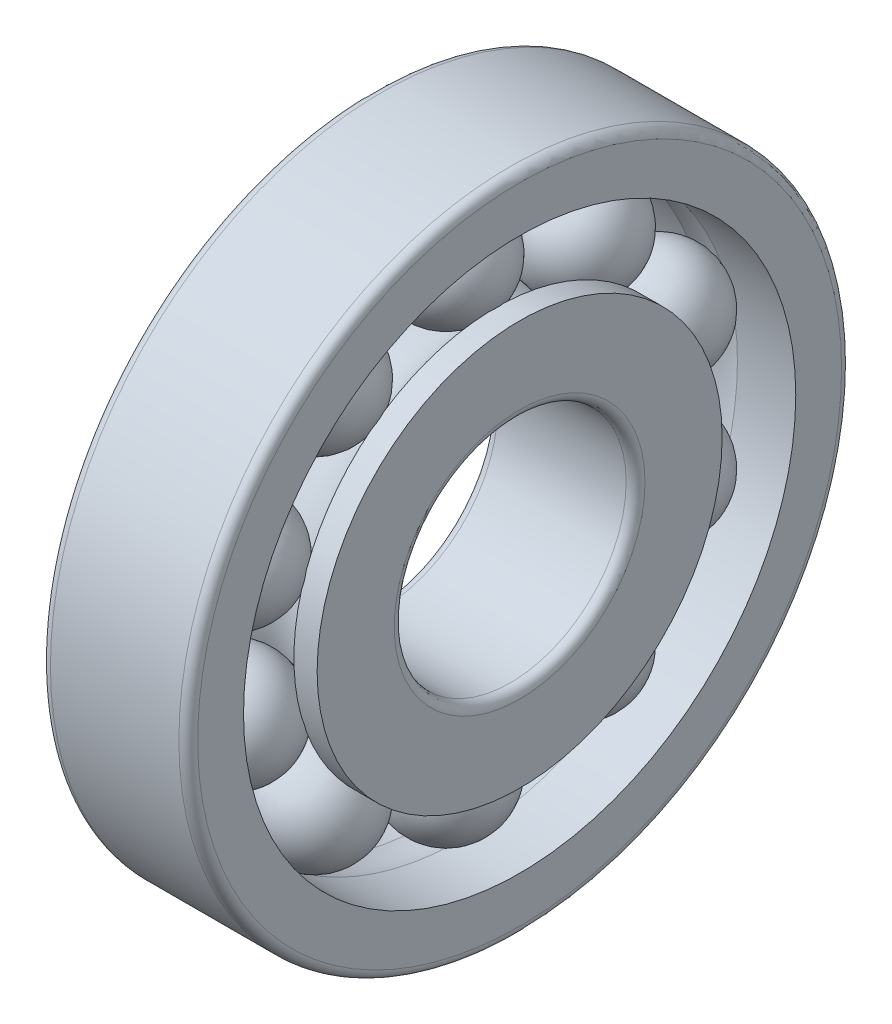
SolidWorks part; units mm, degrees
ref_plane "Plane1" through (0, 0, 0) normal (0, 0, 1) x (1, 0, 0)
ref_plane "Plane2" through (0, 0, 0) normal (0, 1, 0) x (1, 0, 0)
ref_plane "Plane3" through (0, 0, 0) normal (1, 0, 0) x (0, 0, -1)
other "Configuration Table"
sketch "Clipboard" plane through (0, 0, 0) normal (0, 0, 1) x (1, 0, 0)
  line L0 (-10, 0) -> (10, 0) construction
  line L1 (0, 0) -> (22.021, -3.8829)
  line L2 (0, 0) -> (9.4972, 1.6746)
  line L3 (0, 0) -> (-3.8829, -22.021)
  line L4 (0, 0) -> (-22.3573, -0.3902)
  dimension "BallCLRad" = 9.6438
sketch "CagSpiSke" plane through (0, 0, 0) normal (0, 0, 1) x (1, 0, 0)
  line L0 (0.2381, 9.2469) -> (0.2381, 10.0406)
  line L1 (0.2381, 10.0406) -> (-0.2381, 10.0406)
  line L2 (-0.2381, 10.0406) -> (-0.2381, 9.2469)
  line L3 (-0.2381, 9.2469) -> (0.2381, 9.2469)
  line L4 (-20.6375, 0) -> (20.6375, 0) construction
  line L5 (0, 0) -> (0, 23.7692) construction
  dimension "OD" = 20.0813
  dimension "ID" = 18.4937
revolve "CageSpine" add sketch "CagSpiSke" angle 0.001 about L4
ref_axis "Axis1" through (-50, 0, 0) along (1, 0, 0)
sketch "CagBalSke" plane through (0, 0, 0) normal (0, 0, 1) x (1, 0, 0)
  line L0 (-2.6194, 9.6438) -> (2.6194, 9.6438)
  line L1 (-1.905, 9.6438) -> (1.905, 9.6438) construction
  line L2 (-10, 0) -> (10, 0) construction
  line L3 (0, 0) -> (0, 24) construction
  arc A0 (2.6194, 9.6438) -> (-2.6194, 9.6438) centre (0, 9.6438) cw
  dimension "BallCLRad" = 9.6438
revolve "CageBall" [suppressed] add sketch "CagBalSke" angle 360 about L1 reverse direction yes
pattern_circular "CageBalls" [suppressed] count 10 every 36 about axis through (-50, 0, 0) along (1, 0, 0)
sketch "CagTrmODSke" plane through (0, 0, 0) normal (0, 0, 1) x (1, 0, 0)
  line L0 (2.6204, 10.0406) -> (2.6204, 12.2641)
  line L1 (2.6204, 12.2641) -> (-2.6204, 12.2641)
  line L2 (-2.6204, 12.2641) -> (-2.6204, 10.0406)
  line L3 (-2.6204, 10.0406) -> (2.6204, 10.0406)
  line L4 (-20.6375, 0) -> (20.6375, 0) construction
  line L5 (0, 0) -> (0, 25) construction
  dimension "Width" = 5.2408
  dimension "ID" = 20.0813
  dimension "OD" = 24.5282
revolve "CageTrimOD" [suppressed] cut sketch "CagTrmODSke" angle 360 about L4 reverse direction yes
sketch "CagTrmIDSke" plane through (0, 0, 0) normal (0, 0, 1) x (1, 0, 0)
  line L0 (2.6204, 7.0254) -> (2.6204, 9.2469)
  line L1 (2.6204, 9.2469) -> (-2.6204, 9.2469)
  line L2 (-2.6204, 9.2469) -> (-2.6204, 7.0254)
  line L3 (-2.6204, 7.0254) -> (2.6204, 7.0254)
  line L4 (-20.6375, 0) -> (20.6375, 0) construction
  line L5 (0, 0) -> (0, 25) construction
  dimension "Width" = 5.2408
  dimension "ID" = 14.0508
  dimension "OD" = 18.4938
revolve "CageTrimID" [suppressed] cut sketch "CagTrmIDSke" angle 360 about L4 reverse direction yes
sketch "BalSimSke" plane through (0, 0, 0) normal (0, 0, 1) x (1, 0, 0)
  line L0 (-10, 0) -> (10, 0) construction
  line L1 (-10, 9.6438) -> (10, 9.6438) construction
  line L2 (0, 0) -> (0, 23) construction
  circle A0 centre (0, 9.6438) radius 2.3812
  dimension "BallCLRad" = 9.6438
  dimension "Ball_diameter" = 4.7625
revolve "BallsSimplified" [suppressed] add sketch "BalSimSke" angle 360 about L0
sketch "BalDetSke" plane through (0, 0, 0) normal (0, 0, 1) x (1, 0, 0)
  line L0 (-2.3813, 9.6438) -> (2.3813, 9.6438)
  line L1 (-1.905, 9.6438) -> (1.905, 9.6438) construction
  line L2 (0, 0) -> (0, 25) construction
  arc A0 (2.3813, 9.6438) -> (-2.3813, 9.6438) centre (0, 9.6438) cw
  dimension "BallCLRad" = 9.6438
  dimension "Ball_diameter" = 4.7625
revolve "BallDetailed" add sketch "BalDetSke" angle 360 about L1 reverse direction yes
sketch "InnRacSke" plane through (0, 0, 0) normal (0, 0, 1) x (1, 0, 0)
  line L0 (-2.1724, 8.7312) -> (-3.175, 8.7312)
  line L1 (-3.175, 8.7312) -> (-3.175, 5.4064)
  line L2 (-2.7686, 5) -> (2.7686, 5)
  line L3 (3.175, 5.4064) -> (3.175, 8.7312)
  line L4 (3.175, 8.7312) -> (2.1724, 8.7312)
  line L5 (-20.6375, 0) -> (20.6375, 0) construction
  line L6 (0, 0) -> (0, 30) construction
  arc A0 (-3.175, 5.4064) -> (-2.7686, 5) centre (-2.7686, 5.4064) ccw
  arc A1 (2.7686, 5) -> (3.175, 5.4064) centre (2.7686, 5.4064) ccw
  arc A2 (2.1724, 8.7312) -> (-2.1724, 8.7312) centre (0, 9.6438) cw
  dimension "BallCLRad" = 9.6438
  dimension "Fillet_radius" = 0.4064
  dimension "Ball_diameter" = 4.7125
  dimension "ID" = 10
  dimension "OD" = 17.4625
  dimension "Width" = 6.35
revolve "InnerRace" add sketch "InnRacSke" angle 360 about L5 reverse direction yes
sketch "OutRacSke" plane through (0, 0, 0) normal (0, 0, 1) x (1, 0, 0)
  line L0 (-0.658, 11.9063) -> (-3.175, 11.9062)
  line L1 (-3.175, 11.9062) -> (-3.175, 13.8811)
  line L2 (-2.7686, 14.2875) -> (2.7686, 14.2875)
  line L3 (3.175, 13.8811) -> (3.175, 11.9062)
  line L4 (3.175, 11.9062) -> (0.658, 11.9063)
  line L5 (-20.6375, 0) -> (20.6375, 0) construction
  line L6 (0, 0) -> (0, 30) construction
  arc A0 (-3.175, 13.8811) -> (-2.7686, 14.2875) centre (-2.7686, 13.8811) cw
  arc A1 (2.7686, 14.2875) -> (3.175, 13.8811) centre (2.7686, 13.8811) cw
  arc A2 (0.658, 11.9063) -> (-0.658, 11.9063) centre (0, 9.6438) ccw
  dimension "BallCLRad" = 9.6438
  dimension "Fillet_radius" = 0.4064
  dimension "Ball_diameter" = 4.7125
  dimension "Width" = 6.35
revolve "OuterRace" add sketch "OutRacSke" angle 360 about L5 reverse direction yes
pattern_circular "BallsDetailed" count 10 every 36 about axis through (-50, 0, 0) along (1, 0, 0) of "BallDetailed"
equation "\"BallCLRad@Clipboard\" = ( \"OD@OutRacSke\" + \"ID@InnRacSke\" ) / 4"
equation "\"BallCLRad@BalSimSke\" = \"BallCLRad@Clipboard\""
equation "\"BallCLRad@BalDetSke\" = \"BallCLRad@Clipboard\""
equation "\"BallCLRad@InnRacSke\" = \"BallCLRad@Clipboard\""
equation "\"BallCLRad@OutRacSke\" = \"BallCLRad@Clipboard\""
equation "\"Ball_diameter@InnRacSke\" = \"Ball_diameter@BalDetSke\" - 0.05"
equation "\"Ball_diameter@OutRacSke\" = \"Ball_diameter@BalDetSke\" - 0.05"
equation "\"Ball_diameter@BalSimSke\" = \"Ball_diameter@BalDetSke\""
equation "\"Width@OutRacSke\" = \"Width@InnRacSke\""
equation "\"Fillet_radius@OutRacSke\" = \"Fillet_radius@InnRacSke\""
equation "\"Max_count@Clipboard\" = int( 3.14159265 / atn(( \"Ball_diameter@BalDetSke\" / 2) / sqr( \"BallCLRad@Clipboard\"  *  \"BallCLRad@Clipboard\" - ( \"Ball_diameter@BalDetSke\" / 2) *  ( \"Ball_diameter@BalDetSke\" / 2))))"
equation "\"Max_count@Clipboard\" = ((sgn( \"Max_count@Clipboard\" - \"Count@Clipboard\" )-1)*( \"Max_count@Clipboard\" - \"Count@Clipboard\" ))/-2+ \"Count@Clipboard\""
equation "\"Count@BallsDetailed\" = int( \"Show_count@Clipboard\" ) "
equation "\"Count@BallsDetailed\" = ((sgn( \"Count@BallsDetailed\" - \"Max_count@Clipboard\" )-1)*( \"Count@BallsDetailed\" - \"Max_count@Clipboard\" ))/-2+ \"Max_count@Clipboard\""
equation "\"Count@BallsDetailed\" = ((sgn( \"Count@BallsDetailed\" - \"Min_count@Clipboard\" )+1)*( \"Count@BallsDetailed\" - \"Min_count@Clipboard\"))/2 +\"Min_count@Clipboard\""
equation "\"Angle@BallsDetailed\" = 360.0 / \"Max_count@Clipboard\""
equation "\"BallCLRad@CagBalSke\" = \"BallCLRad@Clipboard\""
equation "\"Count@CageBalls\" = \"Count@BallsDetailed\""
equation "\"Angle@CageBalls\" = \"Angle@BallsDetailed\""
equation "\"Angle@CageSpine\" =  \"Angle@CageBalls\" * ( \"Count@CageBalls\" -1 + int( \"Count@CageBalls\" / \"Max_count@Clipboard\" ) )  + 0.001 -  int( \"Count@CageBalls\" / \"Max_count@Clipboard\" ) * 0.001"
equation "\"Angle@CageSpine\" =  \"Angle@CageSpine\" * int( \"Min_count@Clipboard\" / 2) + int(1 / \"Min_count@Clipboard\")  * 0.001"
equation "\"CageWallOD@CagBalSke\" =  \"Ball_diameter@BalDetSke\" * 1.1"
equation "\"Thickness@CagSpiSke\" =  \"Ball_diameter@BalDetSke\" * 0.1"
equation "\"OD@CagTrmODSke\" = \"BallCLRad@Clipboard\" * 2 + \"CageWallOD@CagBalSke\" + 0.002"
equation "\"ID@CagTrmODSke\" = \"BallCLRad@Clipboard\" * 2 + \"Ball_diameter@BalDetSke\" / 6"
equation "\"OD@CagTrmIDSke\" = \"BallCLRad@Clipboard\" * 2 - \"Ball_diameter@BalDetSke\" / 6"
equation "\"ID@CagTrmIDSke\" = \"BallCLRad@Clipboard\" * 2 - \"CageWallOD@CagBalSke\" + 0.002"
equation "\"OD@CagSpiSke\" = \"ID@CagTrmODSke\""
equation "\"ID@CagSpiSke\" = \"OD@CagTrmIDSke\""
equation "\"Width@CagTrmODSke\" = \"CageWallOD@CagBalSke\" + 0.002"
equation "\"Width@CagTrmIDSke\" = \"CageWallOD@CagBalSke\" + 0.002"
